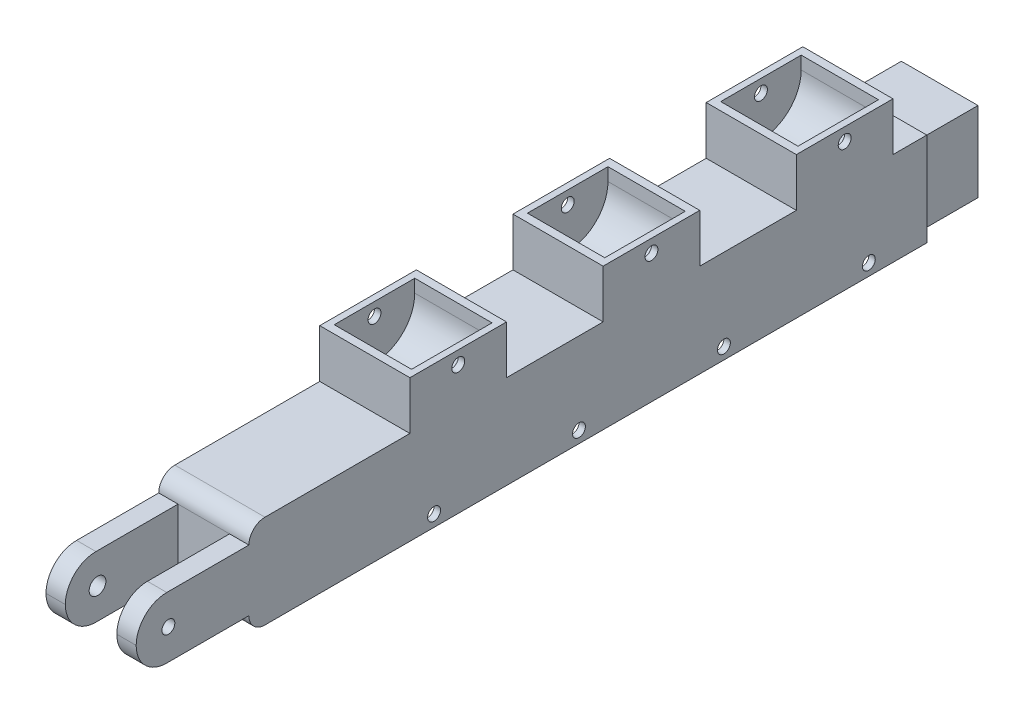
SolidWorks part; units mm, degrees
ref_plane "前视基准面" through (0, 0, 0) normal (0, 0, 1) x (1, 0, 0)
ref_plane "上视基准面" through (0, 0, 0) normal (0, 1, 0) x (1, 0, 0)
ref_plane "右视基准面" through (0, 0, 0) normal (1, 0, 0) x (0, 0, -1)
other "Configuration Table"
sketch "草图1" plane through (0, 0, 0) normal (1, 0, 0) x (0, 0, -1)
  line L0 (-150, 0) -> (150, 0) construction
  line L1 (-125, 14.5) -> (125, 14.5)
  line L2 (-125, 14.5) -> (-125, -14.5)
  line L3 (-125, -14.5) -> (125, -14.5)
  line L4 (125, 14.5) -> (125, -14.5)
  line L5 (-72.5, 29.5) -> (-72.5, 25.5)
  line L6 (-75, 14.5) -> (-45, 14.5)
  line L7 (-75, 14.5) -> (-75, 29.5)
  line L8 (-120, 10.8586) -> (120, 10.8586)
  line L9 (-120, 10.8586) -> (-120, -10.8586)
  line L10 (-120, -10.8586) -> (120, -10.8586)
  line L11 (120, 10.8586) -> (120, -10.8586)
  line L12 (-120, 10.8586) -> (120, -10.8586) construction
  line L13 (-120, -10.8586) -> (120, 10.8586) construction
  line L14 (-75, 29.5) -> (-45, 29.5)
  line L15 (-45, 14.5) -> (-45, 29.5)
  line L16 (-15, 14.5) -> (15, 14.5)
  line L17 (-15, 14.5) -> (-15, 29.5)
  line L18 (-15, 29.5) -> (15, 29.5)
  line L19 (15, 14.5) -> (15, 29.5)
  line L20 (45, 14.5) -> (75, 14.5)
  line L21 (45, 14.5) -> (45, 29.5)
  line L22 (45, 29.5) -> (75, 29.5)
  line L23 (75, 14.5) -> (75, 29.5)
  line L24 (-47.5, 29.5) -> (-47.5, 25.5)
  line L25 (-12.5, 29.5) -> (-12.5, 25.5)
  line L26 (12.5, 29.5) -> (12.5, 25.5)
  line L27 (47.5, 29.5) -> (47.5, 25.5)
  line L29 (72.5, 25.5) -> (72.5, 29.5)
  circle A2 centre (-67.5, -10.8586) radius 2
  circle A3 centre (-22.5, -10.8586) radius 2
  circle A4 centre (22.5, -10.8586) radius 2
  circle A5 centre (-60, 25.5) radius 2
  circle A6 centre (67.5, -10.8586) radius 2
  circle A7 centre (0, 25.5) radius 2
  circle A8 centre (60, 25.5) radius 2
  circle A9 centre (-60, 25.5) radius 12.5
  circle A10 centre (0, 25.5) radius 12.5
  circle A11 centre (60, 25.5) radius 12.5
  circle A12 centre (-67.5, -10.8586) radius 12.5
  circle A13 centre (-22.5, -10.8586) radius 12.5
  circle A14 centre (22.5, -10.8586) radius 12.5
  circle A15 centre (67.5, -10.8586) radius 12.5
  circle A16 centre (150, 0) radius 2
  circle A17 centre (-150, 0) radius 2
  circle A18 centre (-150, 0) radius 2.6
  point P10 (0, 0)
  point P12 (-125, 0)
  point P56 (-60, 29.5)
  point P62 (0, 29.5)
  point P64 (60, 29.5)
  dimension "D2" = 5
  dimension "D4" = 25
  dimension "D8" = 4
  dimension "D18" = 4
  dimension "D22" = 5.2
  dimension "D1" = 300
  dimension "D3" = 5
  dimension "D5" = 14.5
  dimension "D6" = 120
  dimension "D7" = 10.8586
  dimension "D9" = 52.5
  dimension "D10" = 45
  dimension "D11" = 45
  dimension "D12" = 45
  dimension "D13" = 60
  dimension "D14" = 60
  dimension "D15" = 60
  dimension "D16" = 60
  dimension "D17" = 52.5
  dimension "D19" = 30
  dimension "D20" = 4
  dimension "D21" = 15
extrude "凸台-拉伸1" add sketch "草图1" along normal blind 28 contours L1 L4 L3 L2 | L14 L15 L6 L7 | L18 L19 L16 L17 | L22 L23 L20 L21
extrude "切除-拉伸1" cut sketch "草图1<3>" along normal through all contours A2 | A3 | A4 | A6 | A8 | A7 | A5
sketch "草图1<3>" plane through (0, 0, 0) normal (1, 0, 0) x (0, 0, -1) same geometry as "草图1"
extrude "切除-拉伸2" cut sketch "草图1<5>" along normal offset from surface (24 mm away) 2 from offset 2 contours A9 L14 L5 | A9 L24 L14 | A10 L18 L25 | A10 L26 L18 | A11 L22 L27 | A11 L29 L22 | A12 | A9 | A13 | A10 | A14 | A11 | A15 region at (0, 28.5053, 72.3037) region at (0, 28.5053, 47.6963) region at (0, 28.5053, 12.3037) region at (0, 28.5053, -12.3037) region at (0, 28.5053, -47.6963) region at (0, 28.5053, -72.3037) up to face at (28, -10.8586, 65.5)
sketch "草图1<5>" plane through (0, 0, 0) normal (1, 0, 0) x (0, 0, -1) same geometry as "草图1"
sketch "草图3" plane through (0, 0, 125) normal (0, 0, 1) x (1, 0, 0)
  line L0 (28, 14.5) -> (28, -14.5) construction
  line L1 (28, 9.5) -> (22, 9.5)
  line L2 (28, 9.5) -> (28, -9.5)
  line L3 (28, -9.5) -> (22, -9.5)
  line L4 (22, 9.5) -> (22, -9.5)
  line L5 (28, 14.5) -> (0, 14.5) construction
  line L6 (28, -14.5) -> (0, -14.5) construction
  line L7 (0, 14.5) -> (0, -14.5) construction
  line L8 (0, 9.5) -> (6, 9.5)
  line L9 (0, 9.5) -> (0, -9.5)
  line L10 (0, -9.5) -> (6, -9.5)
  line L11 (6, 9.5) -> (6, -9.5)
  dimension "D1" = 6
  dimension "D2" = 5
  dimension "D3" = 5
extrude "凸台-拉伸2" add sketch "草图3" along normal blind 35 contours L1 L4 L3 L2
extrude "凸台-拉伸3" add sketch "草图3<3>" along normal blind 35 contours L2 L3 L4 L1 | L9 L10 L11 L8
sketch "草图3<3>" plane through (0, 0, 125) normal (0, 0, 1) x (1, 0, 0) same geometry as "草图3"
extrude "切除-拉伸3" cut sketch "草图1<6>" along normal through all contours A17
sketch "草图1<6>" plane through (0, 0, 0) normal (1, 0, 0) x (0, 0, -1) same geometry as "草图1"
extrude "切除-拉伸7" cut sketch "草图1<8>" along normal up to next contours A18
sketch "草图1<8>" plane through (0, 0, 0) normal (1, 0, 0) x (0, 0, -1) same geometry as "草图1"
fillet "圆角1" radius 9.5 4 edges at (25, 9.5, 160) (25, -9.5, 160) (3, -9.5, 160) (3, 9.5, 160)
fillet "圆角2" radius 5 2 edges at (14, -14.5, 125) (14, 14.5, 125)
sketch "草图4" plane through (0, 0, -125) normal (0, 0, -1) x (-1, 0, 0)
  line L1 (-28, 14.5) -> (0, 14.5) construction
  circle A0 centre (-14, 0) radius 5.1
  point P7 (-14, 14.5)
  dimension "D1" = 10.2
extrude "切除-拉伸4" cut sketch "草图4" against normal blind 31.5
extrude "切除-拉伸5" cut sketch "草图4<2>" against normal offset from surface (21.5 mm away) 10 flip side to cut up to face at (8.9, 0, -93.5)
sketch "草图4<2>" plane through (0, 0, -125) normal (0, 0, -1) x (-1, 0, 0) same geometry as "草图4"
sketch "草图5" plane through (0, 0, -103.5) normal (0, 0, -1) x (-1, 0, 0)
  line L0 (-28, 14.5) -> (0, 14.5) construction
  line L1 (-25.9, -12.4) -> (-2.1, -12.4)
  line L2 (-25.9, -12.4) -> (-25.9, 12.4)
  line L3 (-25.9, 12.4) -> (-2.1, 12.4)
  line L4 (-2.1, -12.4) -> (-2.1, 12.4)
  line L5 (-25.9, -12.4) -> (-2.1, 12.4) construction
  line L6 (-25.9, 12.4) -> (-2.1, -12.4) construction
  line L7 (0, -14.5) -> (0, 14.5) construction
  circle A0 centre (-14, 0) radius 5.1 construction
  point P0 (-14, 0)
  dimension "D1" = 2.1
  dimension "D2" = 2.1
extrude "切除-拉伸6" cut sketch "草图5" against normal blind 18 flip side to cut contours L3 L4 L1 L2
